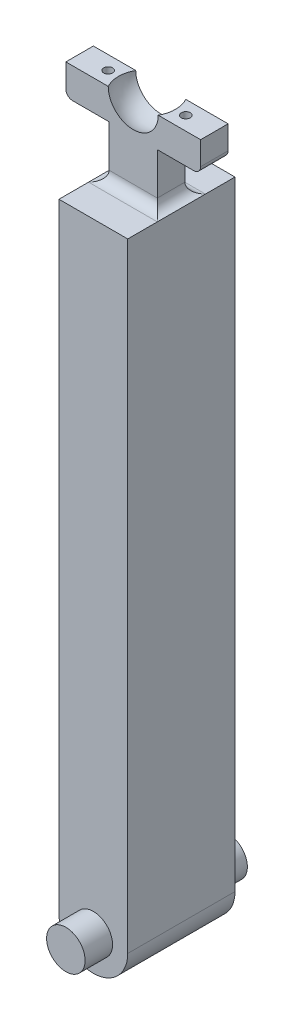
SolidWorks part; units mm, degrees
ref_plane "前视基准面" through (0, 0, 0) normal (0, 0, 1) x (1, 0, 0)
ref_plane "上视基准面" through (0, 0, 0) normal (0, 1, 0) x (1, 0, 0)
ref_plane "右视基准面" through (0, 0, 0) normal (1, 0, 0) x (0, 0, -1)
other "Configuration Table"
sketch "草图1" plane through (0, 0, 0) normal (0, 0, 1) x (1, 0, 0)
  line L0 (-5, 0) -> (5, 0)
  line L1 (5, 0) -> (5, 90)
  line L2 (5, 90) -> (-5, 90)
  line L3 (-5, 90) -> (-5, 0)
  line L7 (0, 0) -> (0, 22.7143) construction
  arc A0 (-5, 0) -> (5, 0) centre (0, 0) ccw
  dimension "D1" = 5
  dimension "D2" = 90
extrude "凸台-拉伸1" add sketch "草图1" along normal mid plane 15.6
sketch "草图4" plane through (0, 0, 7.8) normal (0, 0, 1) x (1, 0, 0)
  circle A0 centre (0, 0) radius 2.8
  dimension "D1" = 5.6
extrude "凸台-拉伸3" add sketch "草图4" along normal blind 4
ref_plane "基准面1" through (0, 102, 0) normal (0, 1, 0) x (1, 0, 0)
sketch "草图5" plane through (0, 102, 0) normal (0, 1, 0) x (1, 0, 0)
  line L1 (-3.5, 2) -> (3.5, 2)
  line L2 (-3.5, 2) -> (-3.5, -2)
  line L3 (-3.5, -2) -> (3.5, -2)
  line L4 (3.5, 2) -> (3.5, -2)
  line L5 (-3.5, 2) -> (3.5, -2) construction
  line L6 (-3.5, -2) -> (3.5, 2) construction
  point P0 (0, 0)
  dimension "D1" = 4
  dimension "D2" = 7
extrude "凸台-拉伸4" add sketch "草图5" against normal up to surface (12 mm away) up to face at (0, 90, 0)
sketch "草图7" plane through (0, 0, 0) normal (0, 0, 1) x (1, 0, 0)
  line L0 (0, 96.9511) -> (0, 94.9196) construction
  line L1 (-9.8, 102) -> (9.8, 102)
  line L2 (-9.8, 102) -> (-9.8, 97.6)
  line L3 (-9.8, 97.6) -> (9.8, 97.6)
  line L4 (9.8, 102) -> (9.8, 97.6)
  line L5 (-3.5, 102) -> (3.5, 102) construction
  dimension "D2" = 4.4
  dimension "D3" = 19.6
extrude "凸台-拉伸5" add sketch "草图7" along normal mid plane 4
sketch "草图8" plane through (0, 97.6, 0) normal (0, -1, 0) x (1, 0, 0)
  line L1 (-4.6108, -1.8) -> (-3.5715, 0)
  line L2 (-3.5715, 0) -> (-4.6108, 1.8)
  line L3 (-4.6108, 1.8) -> (-6.6892, 1.8)
  line L4 (-6.6892, 1.8) -> (-7.7285, 0)
  line L5 (-7.7285, 0) -> (-6.6892, -1.8)
  line L6 (-6.6892, -1.8) -> (-4.6108, -1.8)
  circle A0 centre (-5.65, 0) radius 1.8 construction
  dimension "D1" = 5.65
  dimension "D2" = 3.6
sketch "草图10" plane through (0, 0, 0) normal (0, 0, 1) x (1, 0, 0)
  line L0 (0, 106.15) -> (0, 97.85)
  line L1 (0, 102) -> (-4.15, 102)
  line L2 (-9.8, 102) -> (9.8, 102) construction
  circle A0 centre (0, 102) radius 4.15
  dimension "D2" = 8.3
  dimension "D1" = 90
revolve "切除-旋转1" cut sketch "草图10" angle 360 about L0
mirror "镜向2" about plane through (0, 0, 0) normal (0, 0, 1) of "凸台-拉伸3"
fillet "圆角2" radius 1 2 edges at (9.8, 97.6, 0) (-9.8, 97.6, 0)
hole_wizard "孔1" positions "草图11" profile "草图12" legacy end condition up to next
sketch "草图11" plane through (0, 97.6, 0) normal (0, -1, 0) x (-1, 0, 0)
  point P0 (5.65, 0)
  point P3 (-5.65, 0)
sketch "草图12" plane through (-5.65, 97.6, 0) normal (1, 0, 0) x (0, 0, -1)
  line L0 (0, 0) -> (0, 4.4)
  line L1 (0, 4.4) -> (0.65, 4.4)
  line L2 (0.65, 4.4) -> (0.65, 0)
  line L3 (0.65, 0) -> (0, 0)
  line L4 (0, 110) -> (0, -10) construction
  dimension "直径" = 1.3
  dimension "深度" = 4.4
fillet "圆角3" radius 1.5 4 edges at (3.5, 90, 0) (0, 90, 2) (-3.5, 90, 0) (0, 90, -2)
